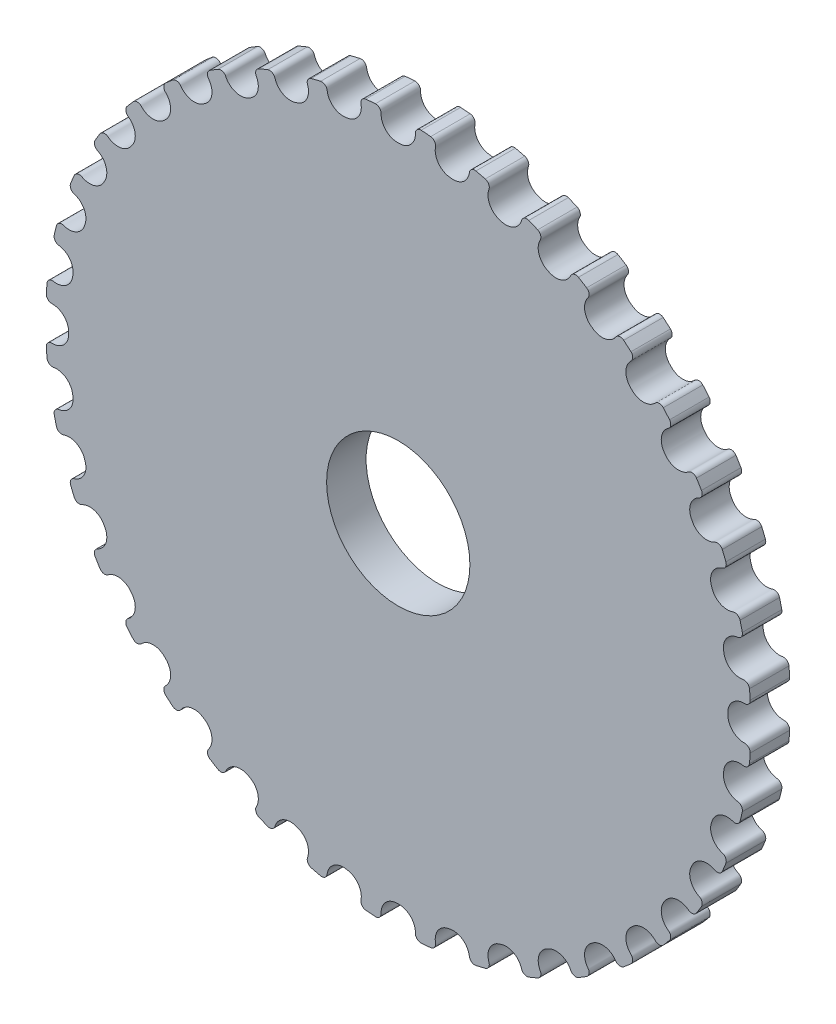
SolidWorks part; units mm, degrees
material "Thornel Mat VMA"
ref_plane "Front Plane" through (0, 0, 0) normal (0, 0, 1) x (1, 0, 0)
ref_plane "Top Plane" through (0, 0, 0) normal (0, 1, 0) x (1, 0, 0)
ref_plane "Right Plane" through (0, 0, 0) normal (1, 0, 0) x (0, 0, -1)
ref_axis "Axis1" through (0, 0, 55) along (0, 0, -1)
sketch "SketchRevolveGearBelt01" plane through (0, 0, 0) normal (1, 0, 0) x (0, 0, -1)
  line L0 (0, 0) -> (1, 0) construction
  line L1 (1.75, 0) -> (1.75, 31.2595)
  line L2 (1.75, 31.2595) -> (-1.75, 31.2595)
  line L3 (-1.75, 31.2595) -> (-1.75, 0)
  line L4 (-1.75, 0) -> (1.75, 0)
  dimension "GearBeltSide1" = 1.75
  dimension "GearBeltOutsideDiameter" = 31.2595
  dimension "GearBeltSide2" = 1.75
revolve "GearBelt01" add sketch "SketchRevolveGearBelt01" angle 360 about L0
sketch "SketchToothGearBelt01" plane through (0, 0, 0) normal (0, 0, 1) x (1, 0, 0)
  arc A0 (31.193, 2.0389) -> (31.193, -2.0389) centre (0, 0) cw
  spline S0 degree 3 poles (31.193, -2.0389) (31.1948, -2.0123) (31.1941, -1.9723) (31.1867, -1.9195) (31.178, -1.8806) (31.1661, -1.8425) (31.1511, -1.8054) (31.1331, -1.7698) (31.1123, -1.7357) (31.0888, -1.7034) (31.0627, -1.6731) (31.0343, -1.6451) (31.0036, -1.6195) (30.971, -1.5965) (30.9365, -1.5763) (30.9006, -1.5589) (30.8633, -1.5445) (30.825, -1.5332) (30.7859, -1.5251) (30.7463, -1.5201) (30.6992, -1.5186) (30.6277, -1.5196) (30.532, -1.516) (30.4198, -1.5026) (30.309, -1.4805) (30.2002, -1.4498) (30.0943, -1.4107) (29.9917, -1.3633) (29.8931, -1.3081) (29.7992, -1.2453) (29.7105, -1.1753) (29.6276, -1.0986) (29.5509, -1.0156) (29.481, -0.9268) (29.4182, -0.8329) (29.363, -0.7343) (29.3157, -0.6317) (29.2767, -0.5257) (29.246, -0.4169) (29.224, -0.3061) (29.2106, -0.1939) (29.2075, -0.1051) (29.2078, -0.0405) (29.2077, 0) (29.2078, 0.0405) (29.2075, 0.1051) (29.2106, 0.1939) (29.224, 0.3061) (29.246, 0.4169) (29.2767, 0.5257) (29.3157, 0.6317) (29.363, 0.7343) (29.4182, 0.8329) (29.481, 0.9268) (29.5509, 1.0156) (29.6276, 1.0986) (29.7105, 1.1753) (29.7992, 1.2453) (29.8931, 1.3081) (29.9917, 1.3633) (30.0943, 1.4107) (30.2002, 1.4498) (30.309, 1.4805) (30.4198, 1.5026) (30.532, 1.516) (30.6277, 1.5196) (30.6992, 1.5186) (30.7463, 1.5201) (30.7859, 1.5251) (30.825, 1.5332) (30.8633, 1.5445) (30.9006, 1.5589) (30.9365, 1.5763) (30.971, 1.5965) (31.0036, 1.6195) (31.0343, 1.6451) (31.0627, 1.6731) (31.0888, 1.7034) (31.1123, 1.7357) (31.1331, 1.7698) (31.1511, 1.8054) (31.1661, 1.8425) (31.178, 1.8806) (31.1867, 1.9195) (31.1941, 1.9723) (31.1948, 2.0123) (31.193, 2.0389) knots 0 0 0 0 0.012476 0.018713 0.024951 0.031189 0.037427 0.043665 0.049903 0.05614 0.062378 0.068616 0.074854 0.081092 0.08733 0.093567 0.099805 0.106043 0.112281 0.118519 0.124756 0.134376 0.152024 0.169672 0.18732 0.204968 0.222616 0.240264 0.257912 0.27556 0.293208 0.310856 0.328503 0.346151 0.363799 0.381447 0.399095 0.416743 0.434391 0.452039 0.469687 0.487335 0.493667 0.5 0.506333 0.512665 0.530313 0.547961 0.565609 0.583257 0.600905 0.618553 0.636201 0.653849 0.671497 0.689144 0.706792 0.72444 0.742088 0.759736 0.777384 0.795032 0.81268 0.830328 0.847976 0.865624 0.875244 0.881481 0.887719 0.893957 0.900195 0.906433 0.91267 0.918908 0.925146 0.931384 0.937622 0.94386 0.950097 0.956335 0.962573 0.968811 0.975049 0.981287 0.987524 1 1 1 1
extrude "ToothExtrudeCutGearBelt01" cut sketch "SketchToothGearBelt01" against normal blind 7.239 and the other way blind 7.239
pattern_circular "PatternGearBelt01" count 40 every 9 about axis through (0, 0, 55) along (0, 0, -1) of "ToothExtrudeCutGearBelt01"
sketch "BoreRevolveSketch" plane through (0, 0, 0) normal (1, 0, 0) x (0, 0, -1)
  line L0 (0, 0) -> (1, 0) construction
  line L1 (-7.239, 0) -> (7.239, 0)
  line L2 (7.239, 0) -> (7.239, 6.35)
  line L3 (7.239, 6.35) -> (-7.239, 6.35)
  line L4 (-7.239, 6.35) -> (-7.239, 0)
  dimension "BoreSide1" = 7.239
  dimension "TaperSide1" = 6.35
  dimension "BoreSide2" = 7.239
  dimension "TaperSide2" = 6.35
revolve "BoreRevolveCut" cut sketch "BoreRevolveSketch" angle 360 about L0
sketch "AuxiliarySketchGearBelt01" plane through (0, 0, 0) normal (0, 0, 1) x (1, 0, 0)
  circle A0 centre (0, 0) radius 31.831 construction
  dimension "PitchDiameter" = 63.6619
